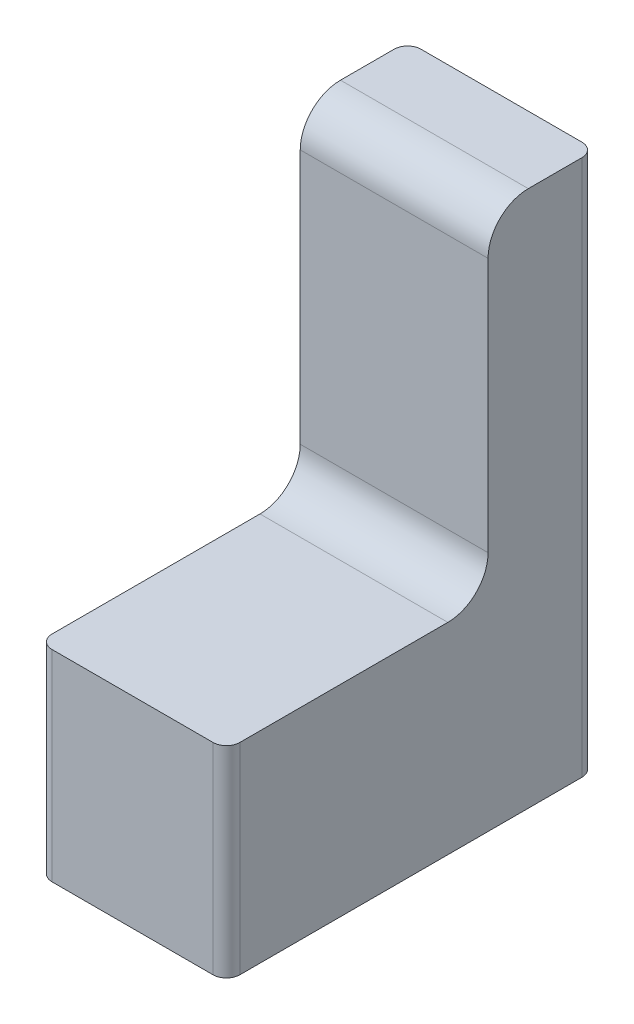
SolidWorks part; units mm, degrees
material "K110"
ref_plane "Front Plane" through (0, 0, 0) normal (0, 0, 1) x (1, 0, 0)
ref_plane "Top Plane" through (0, 0, 0) normal (0, 1, 0) x (1, 0, 0)
ref_plane "Right Plane" through (0, 0, 0) normal (1, 0, 0) x (0, 0, -1)
sketch "Sketch1" plane through (0, 0, 0) normal (0, 1, 0) x (1, 0, 0)
  line L1 (-7, -13.75) -> (7, -13.75)
  line L2 (-7, -13.75) -> (-7, 13.75)
  line L3 (-7, 13.75) -> (7, 13.75)
  line L4 (7, -13.75) -> (7, 13.75)
  line L5 (-7, -13.75) -> (7, 13.75) construction
  line L6 (-7, 13.75) -> (7, -13.75) construction
  point P0 (0, 0)
  dimension "D1" = 27.5
  dimension "D2" = 14
extrude "Boss-Extrude1" add sketch "Sketch1" against normal blind 40
sketch "Sketch2" plane through (7, 0, 0) normal (1, 0, 0) x (0, 0, -1)
  line L0 (13.75, -40) -> (13.75, 0) construction
  line L1 (-13.75, 0) -> (5.75, 0)
  line L2 (-13.75, 0) -> (-13.75, -25)
  line L3 (-13.75, -25) -> (5.75, -25)
  line L4 (5.75, 0) -> (5.75, -25)
  dimension "D1" = 25
  dimension "D2" = 8
extrude "Cut-Extrude1" cut sketch "Sketch2" against normal up to next
fillet "Fillet1" radius 3 2 edges at (0, -25, -5.75) (0, 0, -5.75)
hole_wizard "M6 Tapped Hole1" positions "Sketch8" profile "Sketch4" tap size "M6" standard "ISO"
sketch "Sketch8" plane through (0, -40, 0) normal (0, -1, 0) x (-1, 0, 0)
  line L0 (-7, 13.75) -> (7, 13.75) construction
  line L1 (7, -13.75) -> (-7, -13.75) construction
  point P0 (0, -7.75)
  point P2 (0, 7.75)
  point P5 (0, 0)
  dimension "D1" = 6
  dimension "D2" = 6
sketch "Sketch4" plane through (0, -40, 7.75) normal (1, 0, 0) x (0, 0, -1)
  line L0 (0, 0) -> (0, 13.5022)
  line L1 (0, 13.5022) -> (2.5, 12)
  line L2 (2.5, 12) -> (2.5, 0.525)
  line L3 (2.5, 0.525) -> (3.025, 0)
  line L5 (3.025, 0) -> (0, 0)
  line L6 (-2.5, 0.525) -> (-3.025, 0) construction
  line L10 (0, 13.5022) -> (-2.5, 12) construction
  line L11 (0, -6.35) -> (0, 107.95) construction
  dimension "Tap Drill Dia." = 5
  dimension "Tap Drill Depth" = 12
  dimension "Near C'Sink Dia." = 6.05
  dimension "Near C'Sink Angle" = 90
  dimension "Drill Angle" = 118
cosmetic thread "Hole Thread1"
cosmetic thread "Hole Thread2"
fillet "Fillet2" radius 1 4 edges at (-7, -20, -13.75) (7, -20, -13.75) (7, -32.5, 13.75) (-7, -32.5, 13.75)
